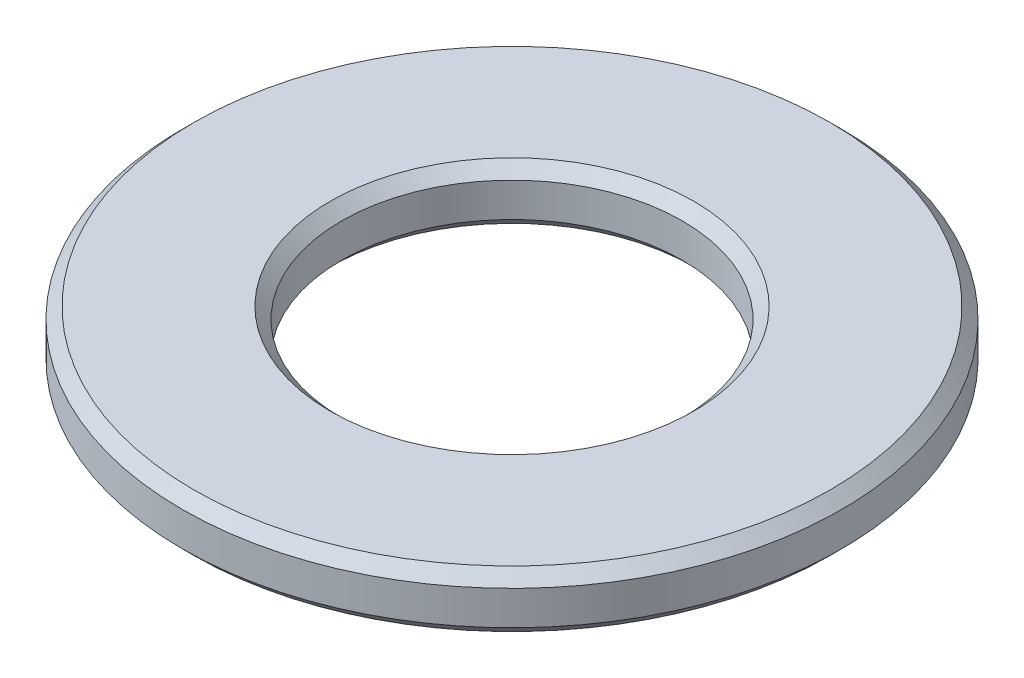
SolidWorks part; units mm, degrees
material "1.4000 (X6Cr13)"
ref_plane "Ebene vorne" through (0, 0, 0) normal (0, 0, 1) x (1, 0, 0)
ref_plane "Ebene oben" through (0, 0, 0) normal (0, 1, 0) x (1, 0, 0)
ref_plane "Ebene rechts" through (0, 0, 0) normal (1, 0, 0) x (0, 0, -1)
sketch "Skizze1" plane through (0, 0, 0) normal (0, 1, 0) x (1, 0, 0)
  circle A0 centre (0, 0) radius 1.5
  circle A1 centre (0, 0) radius 2.9
  dimension "D1" = 3
  dimension "D2" = 5.8
extrude "Aufsatz-Linear austragen1" add sketch "Skizze1" along normal blind 0.5
chamfer "Fase1" distance 0.1 angle 45 4 edges at (0, 0, 2.9) (0, 0, 1.5) (0, 0.5, 1.5) (0, 0.5, 2.9)
ref_axis "Achse1" through (0, -0.025, 0) along (0, 1, 0)
